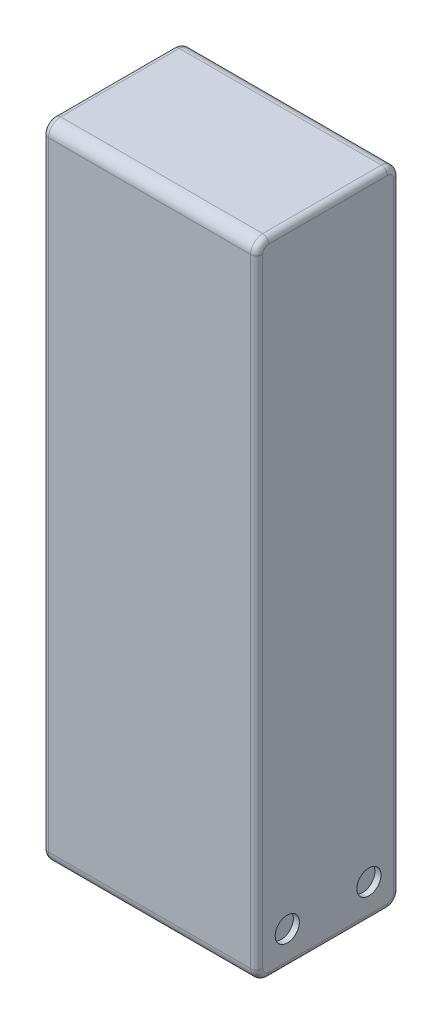
SolidWorks part; units mm, degrees
ref_plane "Front Plane" through (0, 0, 0) normal (0, 0, 1) x (1, 0, 0)
ref_plane "Top Plane" through (0, 0, 0) normal (0, 1, 0) x (1, 0, 0)
ref_plane "Right Plane" through (0, 0, 0) normal (1, 0, 0) x (0, 0, -1)
sketch "Sketch1" plane through (0, 0, 0) normal (0, 1, 0) x (1, 0, 0)
  line L1 (-22.5, -15) -> (22.5, -15)
  line L2 (-22.5, -15) -> (-22.5, 15)
  line L3 (-22.5, 15) -> (22.5, 15)
  line L4 (22.5, -15) -> (22.5, 15)
  line L5 (-22.5, -15) -> (22.5, 15) construction
  line L6 (-22.5, 15) -> (22.5, -15) construction
  point P0 (0, 0)
  dimension "D1" = 45
  dimension "D2" = 30
extrude "Boss-Extrude1" add sketch "Sketch1" along normal mid plane 135
fillet "Fillet1" radius 2.54 4 edges at (0, -67.5, 15) (0, -67.5, -15) (0, 67.5, 15) (0, 67.5, -15)
fillet "Fillet2" radius 1.27 16 edges at (-22.5, 66.7561, -14.2561) (-22.5, 67.5, 0) (-22.5, 66.7561, 14.2561) (-22.5, 0, 15) (-22.5, -66.7561, 14.2561) (-22.5, -67.5, 0) (-22.5, -66.7561, -14.2561) (22.5, 66.7561, -14.2561) (22.5, 67.5, 0) (22.5, 66.7561, 14.2561) (22.5, 0, 15) (22.5, -66.7561, 14.2561) (22.5, -67.5, 0) (22.5, -66.7561, -14.2561) (-22.5, 0, -15) (22.5, 0, -15)
sketch "Sketch2" plane through (22.5, 0, 0) normal (1, 0, 0) x (0, 0, -1)
  line L0 (-8.5725, -60.325) -> (8.5725, -60.325) construction
  circle A0 centre (8.5725, -60.325) radius 2.54
  circle A1 centre (-8.5725, -60.325) radius 2.54
  point P4 (0, -60.325)
  point P5 (8.5725, -60.325)
  dimension "D3" = 5.08
  dimension "D1" = 17.145
  dimension "D2" = 60.325
extrude "Cut-Extrude1" cut sketch "Sketch2" against normal blind 1.27
